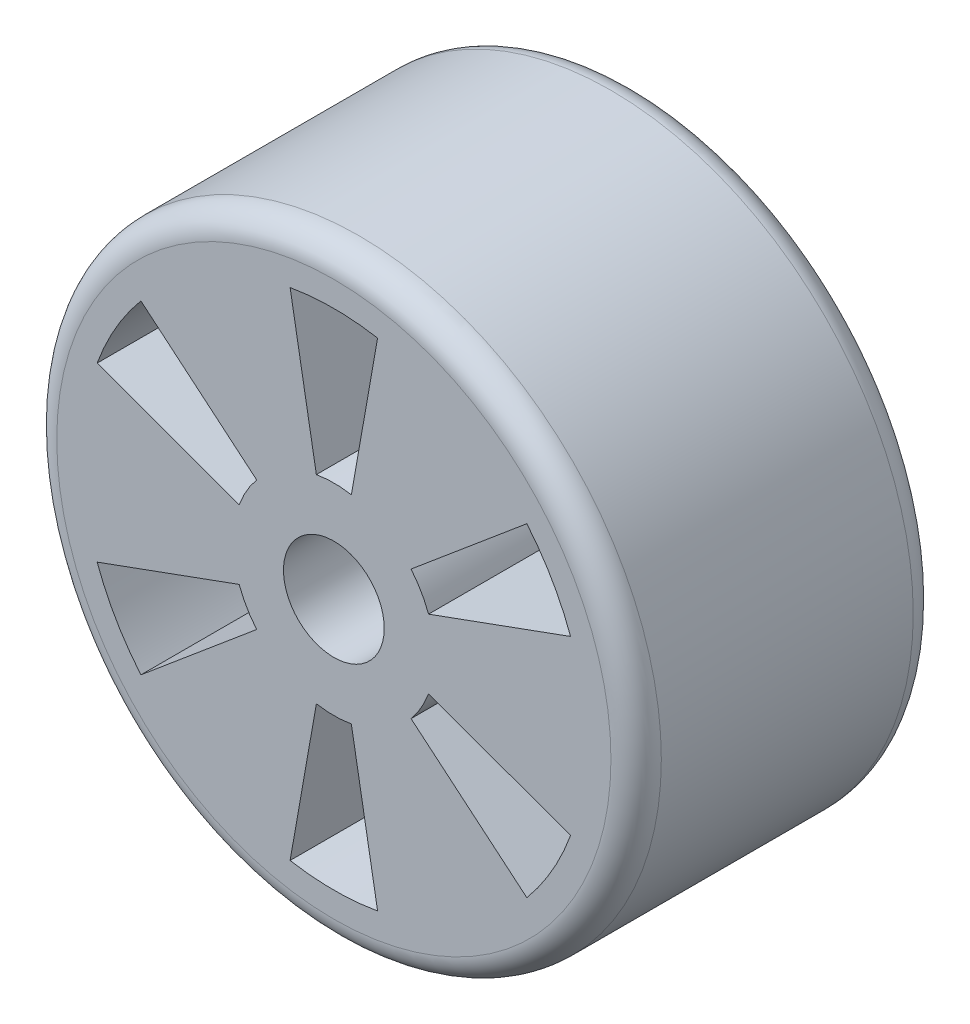
SolidWorks part; units mm, degrees
ref_plane "前视基准面" through (0, 0, 0) normal (0, 0, 1) x (1, 0, 0)
ref_plane "上视基准面" through (0, 0, 0) normal (0, 1, 0) x (1, 0, 0)
ref_plane "右视基准面" through (0, 0, 0) normal (1, 0, 0) x (0, 0, -1)
sketch "草图1" plane through (0, 0, 0) normal (0, 0, 1) x (1, 0, 0)
  circle A0 centre (0, 0) radius 60
  circle A1 centre (0, 0) radius 10
extrude "凸台-拉伸1" add sketch "草图1" against normal blind 60
sketch "草图2" plane through (0, 0, 0) normal (0, 0, 1) x (1, 0, 0)
  line L0 (0, 50) -> (0, 20) construction
  line L1 (-8.6824, 49.2404) -> (-3.473, 19.6962)
  line L2 (8.6824, 49.2404) -> (3.473, 19.6962)
  line L3 (0, 0) -> (0, -60) construction
  circle A0 centre (0, 0) radius 60 construction
  arc A1 (8.6824, 49.2404) -> (-8.6824, 49.2404) centre (0, 0) ccw
  arc A2 (3.473, 19.6962) -> (-3.473, 19.6962) centre (0, 0) ccw
  dimension "D1" = 10
extrude "切除-拉伸1" cut sketch "草图2" against normal blind 60
ref_axis "基准轴1" through (0, 0, -60) along (0, 0, 1)
pattern_circular "阵列(圆周)1" count 6 over 360 about axis through (0, 0, -60) along (0, 0, 1) of "切除-拉伸1"
fillet "圆角1" radius 5 2 edges at (60, 0, -60) (60, 0, 0)
